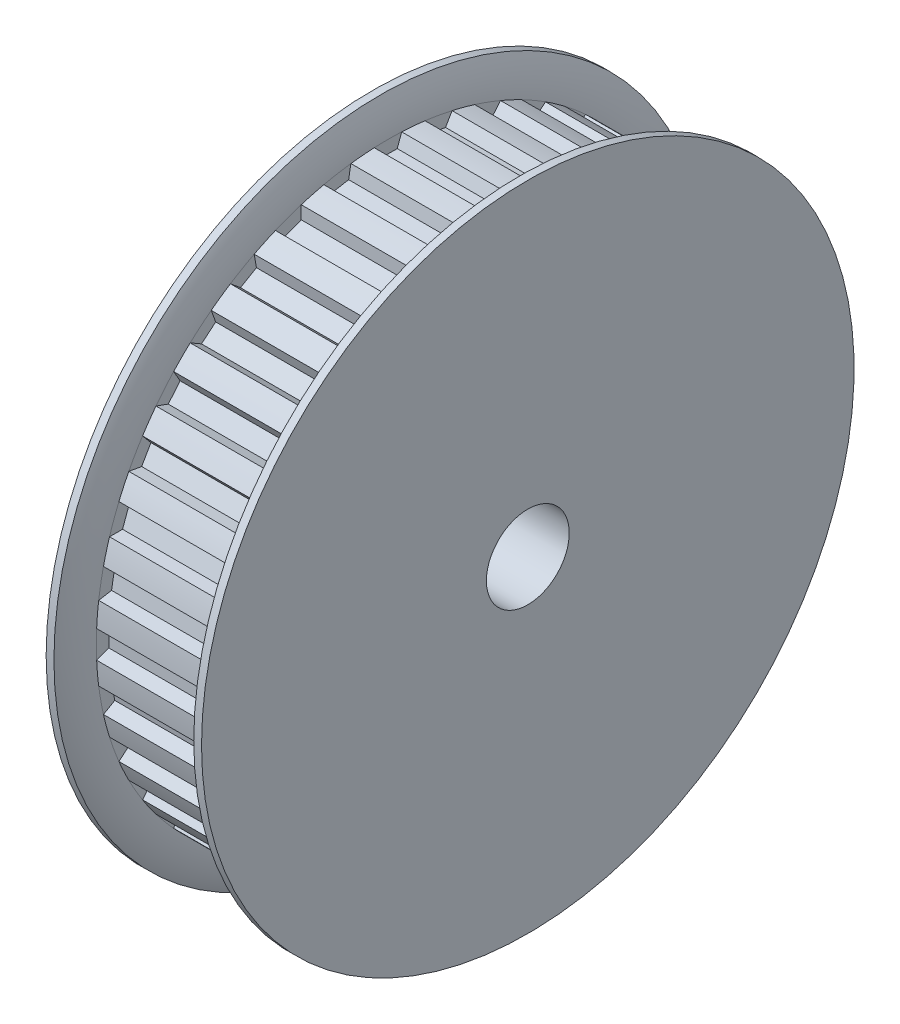
SolidWorks part; units mm, degrees
ref_plane "Front Plane" through (0, 0, 0) normal (0, 0, 1) x (1, 0, 0)
ref_plane "Top Plane" through (0, 0, 0) normal (0, 1, 0) x (1, 0, 0)
ref_plane "Right Plane" through (0, 0, 0) normal (1, 0, 0) x (0, 0, -1)
sketch "Sketch1" plane through (0, 0, 0) normal (1, 0, 0) x (0, 0, -1)
  line L3 (0, 0) -> (0, 26.955) construction
  line L6 (0, 26.955) -> (0, 28.155) construction
  line L7 (-1.325, 28.1238) -> (-0.8942, 26.9402)
  line L8 (1.325, 28.1238) -> (0.8942, 26.9402)
  line L9 (0, -2.2) -> (0, -3.2) construction
  line L10 (0, 28.655) -> (0, 28.155) construction
  line L12 (-0.8942, 26.9402) -> (0.8942, 26.9402)
  line L15 (0, 0) -> (0, -2.2) construction
  circle A0 centre (0, 0) radius 28.655 construction
  circle A1 centre (0, 0) radius 26.955 construction
  arc A7 (1.325, 28.1238) -> (-1.325, 28.1238) centre (0, 0) ccw
  dimension "PD" = 57.31
  dimension "D1" = 40
  dimension "D3" = 0.5
  dimension "D2" = 1.2
  dimension "D4" = 2.65
sketch "Sketch2" plane through (0, 0, 0) normal (0, 0, 1) x (1, 0, 0)
  line L0 (-10.5, 0) -> (10.5, 0) construction
  line L1 (-10.5, 4) -> (10.5, 4)
  line L2 (-10.5, 4) -> (-10.5, 19)
  line L3 (-4.5, 31.5) -> (-3.75, 31.5)
  line L4 (-3, 28.155) -> (-4.5, 28.155) construction
  line L5 (9.75, 28.155) -> (9.75, 31.5) construction
  line L6 (-3, 28.155) -> (9, 28.155)
  line L8 (9, 28.155) -> (10.5, 28.155) construction
  line L9 (9.75, 31.5) -> (10.5, 31.5)
  line L10 (10.5, 31.5) -> (10.5, 4)
  line L12 (-7.5, 19) -> (-7.5, 4) construction
  line L13 (-4.5, 31.5) -> (-4.5, 19)
  line L14 (-4.5, 19) -> (-10.5, 19)
  arc A0 (9, 28.155) -> (9.75, 31.5) centre (16.8344, 28.155) cw
  arc A1 (-3, 28.155) -> (-3.75, 31.5) centre (-10.8344, 28.155) ccw
  point P19 (-3, 28.155)
  point P20 (9, 28.155)
  dimension "Bore Size" = 8
  dimension "Overall Width" = 21
  dimension "Inside Width" = 12
  dimension "Outside Width" = 15
  dimension "Hub Dia" = 38
  dimension "OD" = 63
sketch "Sketch6" plane through (0, 0, 0) normal (0, 0, 1) x (1, 0, 0)
  line L0 (9.75, 31.5) -> (10.5, 31.5) construction
  line L1 (-3, 28.155) -> (9, 28.155) construction
  line L2 (-4.5, 31.5) -> (-3.75, 31.5) construction
  line L3 (-4.5, 31.5) -> (-4.5, 19) construction
  line L4 (-4.5, 19) -> (-10.5, 19) construction
  line L5 (-10.5, 4) -> (-10.5, 19) construction
  line L6 (-10.5, 4) -> (10.5, 4) construction
  line L7 (10.5, 31.5) -> (10.5, 4) construction
  line L8 (9.75, 31.5) -> (10.5, 31.5)
  line L9 (-3, 28.155) -> (9, 28.155)
  line L10 (-4.5, 31.5) -> (-3.75, 31.5)
  line L11 (-4.5, 31.5) -> (-4.5, 19)
  line L12 (-4.5, 19) -> (-10.5, 19)
  line L13 (-10.5, 4) -> (-10.5, 19)
  line L14 (-10.5, 4) -> (10.5, 4)
  line L15 (10.5, 31.5) -> (10.5, 4)
  arc A0 (9.75, 31.5) -> (9, 28.155) centre (16.8344, 28.155) ccw construction
  arc A1 (-3, 28.155) -> (-3.75, 31.5) centre (-10.8344, 28.155) ccw construction
  arc A2 (9.75, 31.5) -> (9, 28.155) centre (16.8344, 28.155) ccw
  arc A3 (-3, 28.155) -> (-3.75, 31.5) centre (-10.8344, 28.155) ccw
revolve "Revolve1" add sketch "Sketch6" angle 360 about L0
sketch "Sketch3" plane through (0, 0, 0) normal (1, 0, 0) x (0, 0, -1)
  line L2 (-1.325, 28.1238) -> (-0.8942, 26.9402) construction
  line L3 (-0.8942, 26.9402) -> (0.8942, 26.9402) construction
  line L4 (1.325, 28.1238) -> (0.8942, 26.9402) construction
  line L5 (-1.325, 28.1238) -> (-0.8942, 26.9402)
  line L6 (-0.8942, 26.9402) -> (0.8942, 26.9402)
  line L7 (1.325, 28.1238) -> (0.8942, 26.9402)
  arc A1 (1.325, 28.1238) -> (-1.325, 28.1238) centre (0, 0) ccw construction
  arc A2 (1.325, 28.1238) -> (-1.325, 28.1238) centre (0, 0) ccw
extrude "Cut-Extrude1" cut sketch "Sketch3" along normal up to vertex (9 mm away) from vertex up to point (9, 28.155, 0) starting at point (-3, 28.155, 0)
pattern_circular "CirPattern1" count 36 over 360 about axis through (-10.5, 0, 0) along (-1, 0, 0) of "Cut-Extrude1"
sketch "Sketch5" plane through (0, 0, 0) normal (0, 0, 1) x (1, 0, 0)
  line L0 (-10.5, 0) -> (10.5, 0) construction
  point P0 (9, 0)
ref_axis "Center Axis 1" through (10.5, 0, 0) along (-1, 0, 0)
equation "\"D3@Sketch1\" = \"ht@Sketch1\" / 2"
equation "\"D2@Sketch1\" = \"hs@Sketch1\" - \"ht@Sketch1\""
